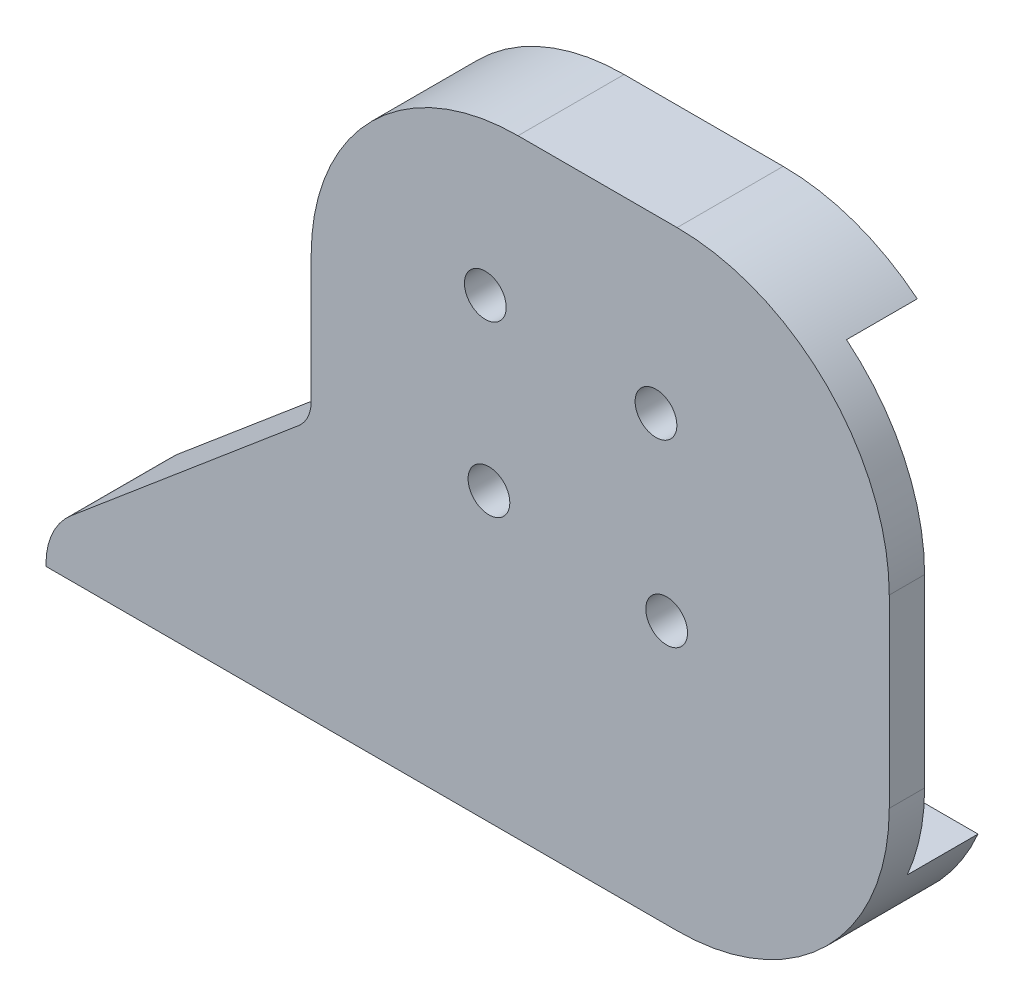
SolidWorks part; units mm, degrees
ref_plane "Front Plane" through (0, 0, 0) normal (0, 0, 1) x (1, 0, 0)
ref_plane "Top Plane" through (0, 0, 0) normal (0, 1, 0) x (1, 0, 0)
ref_plane "Right Plane" through (0, 0, 0) normal (1, 0, 0) x (0, 0, -1)
sketch "Sketch4" plane through (0, 0, 0) normal (0, 0, 1) x (1, 0, 0)
  line L4 (-3.3683, -14.4931) -> (-3.3683, -8.3263)
  line L31 (34.7317, -14.4931) -> (34.7317, 16.6219)
  line L32 (34.7317, 16.6219) -> (8.0617, 16.6219)
  line L33 (-3.3683, 5.1919) -> (-3.3683, -14.4931)
  line L41 (-3.3683, -8.3263) -> (-3.3683, 5.1919)
  line L42 (-6.7973, 5.1919) -> (-6.7973, -14.4931)
  line L43 (31.3027, 13.1929) -> (8.0617, 13.1929)
  line L44 (31.3027, -11.0641) -> (31.3027, 13.1929)
  line L45 (31.3027, -11.0641) -> (-3.3683, -11.0641)
  line L46 (34.7317, -14.4931) -> (-3.3683, -14.4931)
  line L47 (34.7317, -17.9221) -> (-3.3683, -17.9221)
  line L49 (34.7317, 20.0509) -> (8.0617, 20.0509)
  line L50 (-6.7973, -14.4931) -> (-6.7973, -17.9221)
  line L51 (-6.7973, -17.9221) -> (-3.3683, -17.9221)
  line L52 (34.7317, -17.9221) -> (-6.7973, -17.9221)
  line L54 (-6.7973, -17.9221) -> (-6.7973, -21.1606)
  line L56 (-6.7973, -5.1052) -> (-25.8473, -21.1606)
  line L57 (-25.8473, -21.1606) -> (-6.7973, -21.1606)
  line L58 (34.7317, -17.9221) -> (34.7317, 20.0509)
  line L59 (38.1607, 20.0509) -> (8.0617, 20.0509) construction
  line L60 (38.1607, -17.9221) -> (38.1607, 20.0509) construction
  line L61 (38.1607, -17.9221) -> (-3.3683, -17.9221) construction
  line L62 (-6.7973, -21.1606) -> (34.7317, -21.1606)
  line L63 (-6.7973, -21.1606) -> (-6.7973, -17.9221)
  line L64 (34.7317, -21.1606) -> (34.7317, -17.9221)
  line L65 (-6.7973, -17.9221) -> (34.7317, -17.9221)
  arc A13 (8.0617, 16.6219) -> (-3.3683, 5.1919) centre (8.0617, 5.1919) ccw
  circle A14 centre (5.9732, -3.082) radius 1.5
  circle A15 centre (18.7421, -4.7947) radius 1.5
  circle A16 centre (17.9732, 7.7333) radius 1.5
  circle A17 centre (5.7127, 8.9496) radius 1.5
  arc A18 (8.0617, 13.1929) -> (0.0607, 5.1919) centre (8.0617, 5.1919) ccw
  arc A19 (8.0617, 20.0509) -> (-6.7973, 5.1919) centre (8.0617, 5.1919) ccw
  point P4 (-83.82, -3.81)
  point P7 (-43.18, -3.81)
  dimension "D1" = 3.429
  dimension "D2" = 3.429
  dimension "D3" = 19.05
  dimension "D4" = 3.2385
extrude "Boss-Extrude1" add sketch "Sketch4" against normal blind 7.62 contours L49 A19 L42 L50 L51 L47 L58 L46 L4 L33 A13 L32 | L56 L57 L54 L50 L42 | L62 L64 L47 L51 L54
extrude "Boss-Extrude2" add sketch "Sketch4<3>" against normal blind 2.54 contours L31 A17 A16 region at (16.181, 0.713, 0)
sketch "Sketch4<3>" plane through (0, 0, 0) normal (0, 0, 1) x (1, 0, 0) same geometry as "Sketch4"
sketch "Sketch5" plane through (0, -21.1606, 0) normal (0, -1, 0) x (1, 0, 0)
  line L4 (34.7317, 0) -> (-25.8473, 0)
  line L5 (-25.8473, 0) -> (-25.8473, -7.62)
  line L6 (-25.8473, -7.62) -> (34.7317, -7.62)
  line L7 (34.7317, -7.62) -> (34.7317, 0)
  line L8 (34.7317, 0) -> (-25.8473, 0)
  line L9 (-25.8473, 0) -> (-25.8473, -7.62)
  line L10 (-25.8473, -7.62) -> (34.7317, -7.62)
  line L11 (34.7317, -7.62) -> (34.7317, 0)
  dimension "D1" = 0
extrude "Boss-Extrude3" add sketch "Sketch5" along normal blind 2.54
fillet "Fillet1" radius 15.24 2 edges at (34.7317, 20.0509, -3.81) (34.7317, -23.7006, -3.81)
fillet "Fillet2" radius 5.08 1 edges at (-25.8473, -21.1606, -3.81)
fillet "Fillet3" radius 2.54 1 edges at (-6.7973, -5.1052, -3.81)
